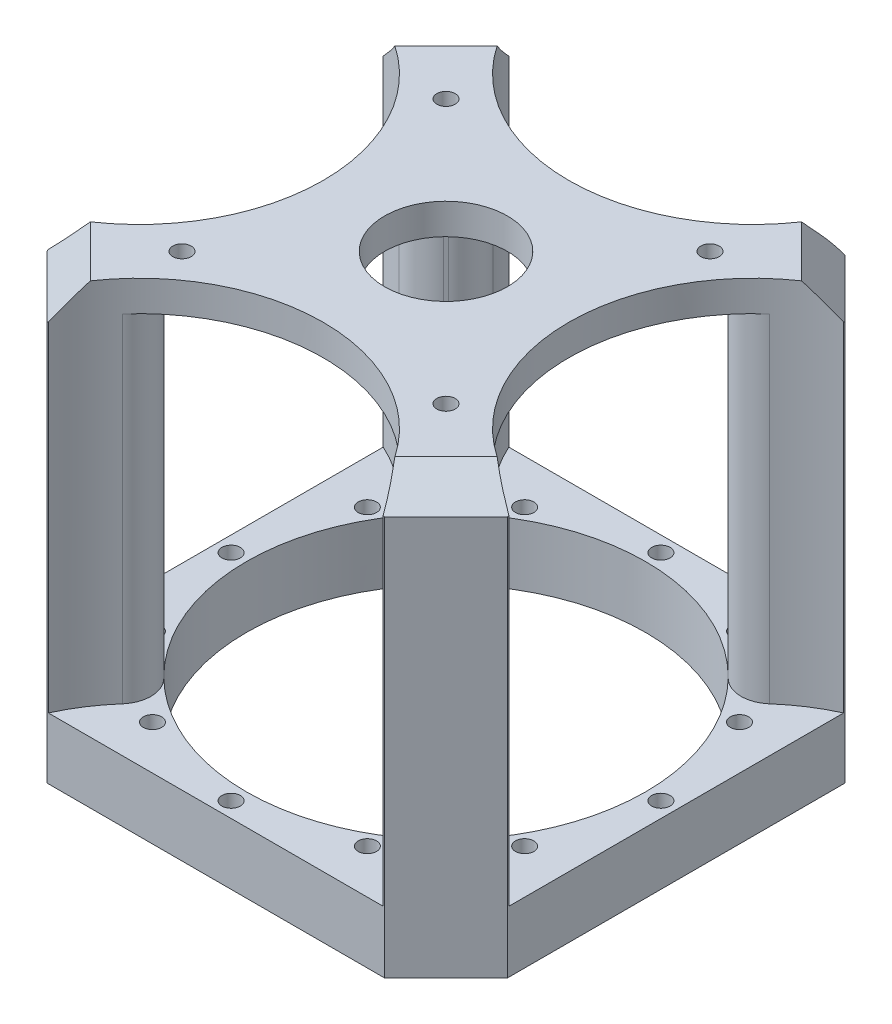
SolidWorks part; units mm, degrees
ref_plane "Front Plane" through (0, 0, 0) normal (0, 0, 1) x (1, 0, 0)
ref_plane "Top Plane" through (0, 0, 0) normal (0, 1, 0) x (1, 0, 0)
ref_plane "Right Plane" through (0, 0, 0) normal (1, 0, 0) x (0, 0, -1)
sketch "Sketch1" plane through (0, 0, 0) normal (0, 1, 0) x (1, 0, 0)
  line L1 (-37.5, -37.5) -> (37.5, -37.5)
  line L2 (-37.5, -37.5) -> (-37.5, 37.5)
  line L3 (-37.5, 37.5) -> (37.5, 37.5)
  line L4 (37.5, -37.5) -> (37.5, 37.5)
  line L5 (-37.5, -37.5) -> (37.5, 37.5) construction
  line L6 (-37.5, 37.5) -> (37.5, -37.5) construction
  circle A0 centre (0, 0) radius 37.5 construction
  circle A1 centre (0, 0) radius 32.5
  circle A2 centre (0, 0) radius 35 construction
  circle A3 centre (0, 35) radius 1.5
  circle A4 centre (17.5, 30.3109) radius 1.5
  circle A5 centre (30.3109, 17.5) radius 1.5
  circle A6 centre (35, 0) radius 1.5
  circle A7 centre (30.3109, -17.5) radius 1.5
  circle A8 centre (17.5, -30.3109) radius 1.5
  circle A9 centre (0, -35) radius 1.5
  circle A10 centre (-17.5, -30.3109) radius 1.5
  circle A11 centre (-30.3109, -17.5) radius 1.5
  circle A12 centre (-35, 0) radius 1.5
  circle A13 centre (-30.3109, 17.5) radius 1.5
  circle A14 centre (-17.5, 30.3109) radius 1.5
  point P35 (0, 0)
  dimension "D1" = 75
  dimension "D2" = 65
  dimension "D3" = 70
  dimension "D4" = 3
  dimension "D5" = 12
extrude "Boss-Extrude1" add sketch "Sketch1" along normal blind 65
sketch "Sketch2" plane through (0, 65, 0) normal (0, 1, 0) x (1, 0, 0)
  line L1 (-37.5, -37.5) -> (37.5, -37.5)
  line L2 (-37.5, -37.5) -> (-37.5, 37.5)
  line L3 (-37.5, 37.5) -> (37.5, 37.5)
  line L4 (37.5, -37.5) -> (37.5, 37.5)
  line L5 (-37.5, -37.5) -> (37.5, 37.5) construction
  line L6 (-37.5, 37.5) -> (37.5, -37.5) construction
  line L7 (-21.5, -21.5) -> (21.5, -21.5) construction
  line L8 (-21.5, -21.5) -> (-21.5, 21.5) construction
  line L9 (-21.5, 21.5) -> (21.5, 21.5) construction
  line L10 (21.5, -21.5) -> (21.5, 21.5) construction
  line L11 (-21.5, -21.5) -> (21.5, 21.5) construction
  line L12 (-21.5, 21.5) -> (21.5, -21.5) construction
  circle A0 centre (0, 0) radius 35 construction
  circle A1 centre (0, 35) radius 1.5
  circle A2 centre (17.5, 30.3109) radius 1.5
  circle A3 centre (30.3109, 17.5) radius 1.5
  circle A4 centre (35, 0) radius 1.5
  circle A5 centre (30.3109, -17.5) radius 1.5
  circle A6 centre (17.5, -30.3109) radius 1.5
  circle A7 centre (0, -35) radius 1.5
  circle A8 centre (-17.5, -30.3109) radius 1.5
  circle A9 centre (-30.3109, -17.5) radius 1.5
  circle A10 centre (-35, 0) radius 1.5
  circle A11 centre (-30.3109, 17.5) radius 1.5
  circle A12 centre (-17.5, 30.3109) radius 1.5
  circle A13 centre (0, 0) radius 10
  circle A14 centre (-21.5, 21.5) radius 1.5
  circle A15 centre (21.5, 21.5) radius 1.5
  circle A16 centre (21.5, -21.5) radius 1.5
  circle A17 centre (-21.5, -21.5) radius 1.5
  point P0 (0, 0)
  point P37 (0, 0)
  dimension "D1" = 70
  dimension "D3" = 20
  dimension "D4" = 43
  dimension "D2" = 12
extrude "Boss-Extrude2" add sketch "Sketch2" along normal blind 5
sketch "Sketch3" plane through (0, 70, 0) normal (0, 1, 0) x (1, 0, 0)
  line L0 (0, 0) -> (0, 50) construction
  circle A0 centre (0, 50) radius 30
  dimension "D2" = 60
  dimension "D1" = 50
extrude "Cut-Extrude1" cut sketch "Sketch3" against normal blind 60
pattern_circular "CirPattern1" count 4 over 360 about axis through (0, 65, 0) along (0, -1, 0) of "Cut-Extrude1" reverse direction yes
fillet "Fillet2" radius 5.1 9 edges at (26.5625, 37.5, 18.7265) (26.5625, 37.5, -18.7265) (-18.7265, 37.5, 26.5625) (18.7265, 37.5, 26.5625) (27.2718, 40, -37.5) (-26.5625, 37.5, -18.7265) (-26.5625, 37.5, 18.7265) (-18.7265, 37.5, -26.5625) (18.7265, 37.5, -26.5625)
chamfer "Chamfer1" distance 10 angle 45 4 edges at (37.5, 35, 37.5) (37.5, 35, -37.5) (-37.5, 35, -37.5) (-37.5, 35, 37.5)
chamfer "Chamfer2" distance 5 angle 45 4 edges at (-32.5, 70, 32.5) (32.5, 70, 32.5) (32.7775, 70, -32.2225) (-32.5, 70, -32.5)
